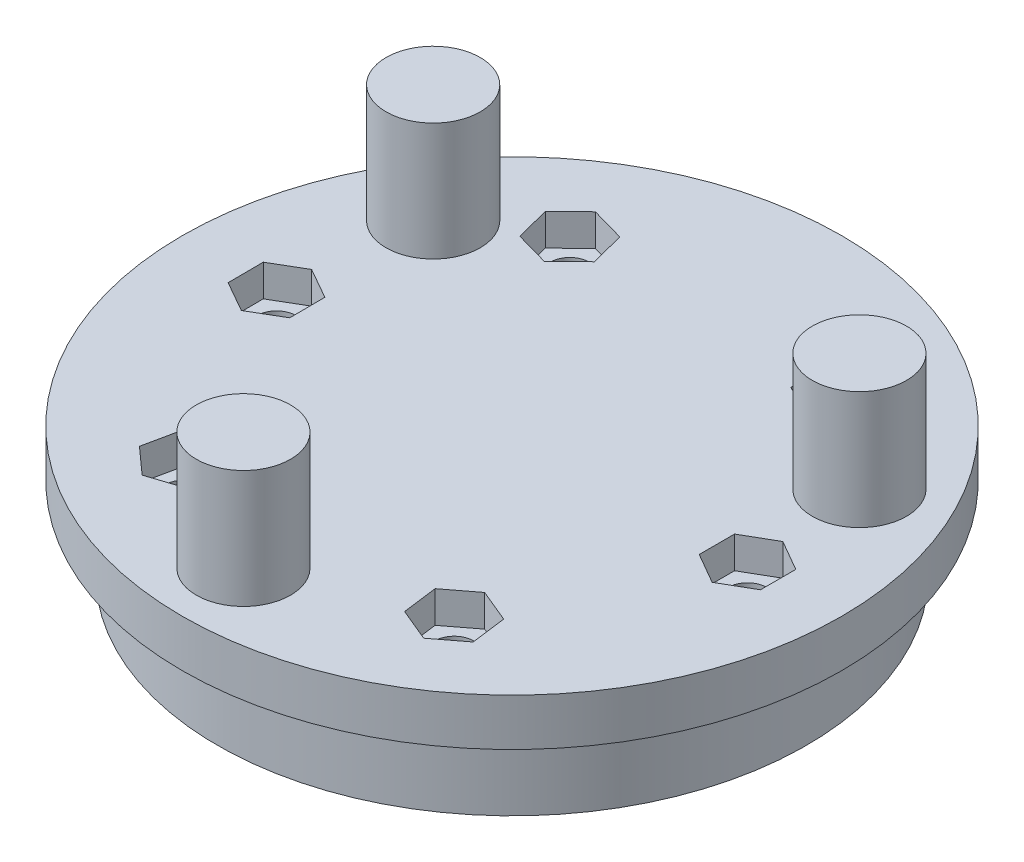
SolidWorks part; units mm, degrees
ref_plane "Front Plane" through (0, 0, 0) normal (0, 0, 1) x (1, 0, 0)
ref_plane "Top Plane" through (0, 0, 0) normal (0, 1, 0) x (1, 0, 0)
ref_plane "Right Plane" through (0, 0, 0) normal (1, 0, 0) x (0, 0, -1)
sketch "Sketch3" plane through (0, 0, 0) normal (0, 1, 0) x (1, 0, 0)
  circle A0 centre (0, 0) radius 28
  dimension "D1" = 56
extrude "Boss-Extrude1" add sketch "Sketch3" along normal blind 4
sketch "Sketch6" plane through (0, 0, 0) normal (0, -1, 0) x (1, 0, 0)
  circle A0 centre (0, 0) radius 25
  dimension "D1" = 50
extrude "Boss-Extrude4" add sketch "Sketch6" along normal blind 7
sketch "Sketch7" plane through (0, 4, 0) normal (0, 1, 0) x (1, 0, 0)
  line L0 (0, 0) -> (28, 0) construction
  line L1 (0, 0) -> (-17.3949, 11.0818) construction
  line L2 (0, 0) -> (-0.9542, -21.8542) construction
  line L3 (0, 0) -> (24.8363, 12.929) construction
  circle A0 centre (0, 0) radius 28 construction
  circle A8 centre (-0.9542, -21.8542) radius 4
  circle A9 centre (-18.4492, 11.7534) radius 4
  circle A10 centre (19.4034, 10.1008) radius 4
  point P17 (0, 0)
  dimension "D4" = 3
  dimension "D7" = 27.5
  dimension "D3" = 8
  dimension "D2" = 120
  dimension "D1" = 120
extrude "Boss-Extrude5" add sketch "Sketch7" along normal blind 10
sketch "Sketch8" plane through (0, 0, 0) normal (0, -1, 0) x (1, 0, 0)
  line L0 (0, 0) -> (20, 0) construction
  line L1 (0, 25) -> (0, -25) construction
  line L2 (0, 0) -> (11.4715, 16.383) construction
  line L3 (0, 0) -> (11.4715, -16.383) construction
  line L4 (0, 0) -> (-13.6508, -19.4954) construction
  line L5 (0, 0) -> (-20, 0) construction
  line L6 (0, 0) -> (-11.4715, -16.383) construction
  line L7 (0, 0) -> (-11.4715, 16.383) construction
  circle A0 centre (20, 0) radius 1.65
  circle A1 centre (0, 0) radius 25 construction
  circle A2 centre (0, 0) radius 25 construction
  circle A3 centre (-20, 0) radius 1.65
  circle A4 centre (11.4715, 16.383) radius 1.65
  circle A5 centre (-11.4715, -16.383) radius 1.65
  circle A6 centre (11.4715, -16.383) radius 1.65
  circle A7 centre (-11.4715, 16.383) radius 1.65
  dimension "D1" = 55
  dimension "D2" = 55
  dimension "D3" = 35
  dimension "D4" = 55
  dimension "D5" = 35
extrude "Cut-Extrude1" cut sketch "Sketch8" against normal through all and the other way blind 10
sketch "Sketch11" plane through (0, 4, 0) normal (0, 1, 0) x (1, 0, 0)
  line L1 (11.8581, -19.3603) -> (14.2432, -17.5369)
  line L2 (14.2432, -17.5369) -> (13.8566, -14.5597)
  line L3 (13.8566, -14.5597) -> (11.085, -13.4058)
  line L4 (11.085, -13.4058) -> (8.6999, -15.2292)
  line L5 (8.6999, -15.2292) -> (9.0865, -18.2064)
  line L6 (9.0865, -18.2064) -> (11.8581, -19.3603)
  line L7 (-12.0914, -19.3206) -> (-9.2375, -18.3886)
  line L8 (-9.2375, -18.3886) -> (-8.6176, -15.4511)
  line L9 (-8.6176, -15.4511) -> (-10.8516, -13.4455)
  line L10 (-10.8516, -13.4455) -> (-13.7056, -14.3774)
  line L11 (-13.7056, -14.3774) -> (-14.3254, -17.315)
  line L12 (-14.3254, -17.315) -> (-12.0914, -19.3206)
  line L13 (-22.5906, -1.5173) -> (-19.9813, -3.0022)
  line L14 (-19.9813, -3.0022) -> (-17.3907, -1.4849)
  line L15 (-17.3907, -1.4849) -> (-17.4094, 1.5173)
  line L16 (-17.4094, 1.5173) -> (-20.0187, 3.0022)
  line L17 (-20.0187, 3.0022) -> (-22.6093, 1.4849)
  line L18 (-22.6093, 1.4849) -> (-22.5906, -1.5173)
  line L19 (20, -3.0022) -> (22.6, -1.5011)
  line L20 (22.6, -1.5011) -> (22.6, 1.5011)
  line L21 (22.6, 1.5011) -> (20, 3.0022)
  line L22 (20, 3.0022) -> (17.4, 1.5011)
  line L23 (17.4, 1.5011) -> (17.4, -1.5011)
  line L24 (17.4, -1.5011) -> (20, -3.0022)
  line L25 (9.0083, 14.6668) -> (11.7262, 13.3916)
  line L26 (11.7262, 13.3916) -> (14.1895, 15.1079)
  line L27 (14.1895, 15.1079) -> (13.9348, 18.0993)
  line L28 (13.9348, 18.0993) -> (11.2168, 19.3744)
  line L29 (11.2168, 19.3744) -> (8.7536, 17.6582)
  line L30 (8.7536, 17.6582) -> (9.0083, 14.6668)
  line L31 (-10.7297, 13.4739) -> (-8.5812, 15.5709)
  line L32 (-8.5812, 15.5709) -> (-9.3231, 18.48)
  line L33 (-9.3231, 18.48) -> (-12.2134, 19.2922)
  line L34 (-12.2134, 19.2922) -> (-14.3618, 17.1952)
  line L35 (-14.3618, 17.1952) -> (-13.62, 14.286)
  line L36 (-13.62, 14.286) -> (-10.7297, 13.4739)
  circle A0 centre (11.4715, -16.383) radius 2.6 construction
  circle A1 centre (-11.4715, -16.383) radius 2.6 construction
  circle A2 centre (-20, 0) radius 2.6 construction
  circle A3 centre (20, 0) radius 2.6 construction
  circle A4 centre (11.4715, 16.383) radius 2.6 construction
  circle A5 centre (-11.4715, 16.383) radius 2.6 construction
  dimension "D1" = 5.2
extrude "Cut-Extrude3" cut sketch "Sketch11" against normal blind 2.7
